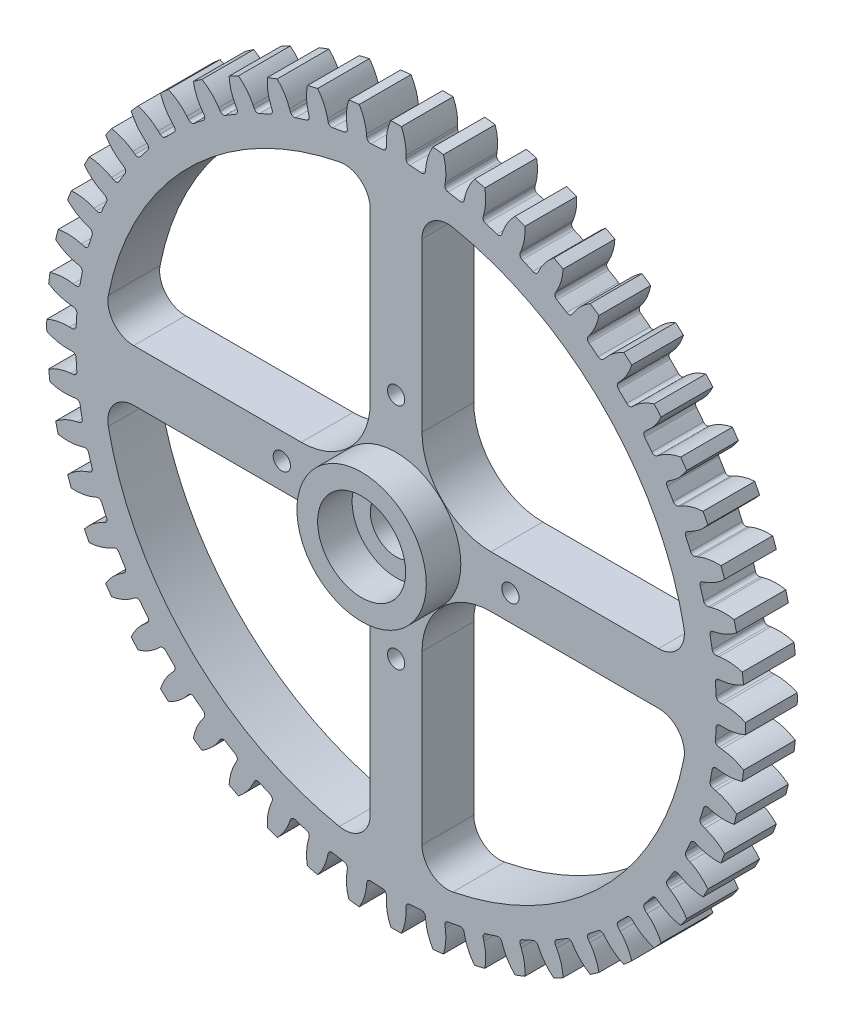
SolidWorks part; units mm, degrees
ref_plane "Front Plane" through (0, 0, 0) normal (0, 0, 1) x (1, 0, 0)
ref_plane "Top Plane" through (0, 0, 0) normal (0, 1, 0) x (1, 0, 0)
ref_plane "Right Plane" through (0, 0, 0) normal (1, 0, 0) x (0, 0, -1)
sketch "Esquisse1" plane through (0, 0, 0) normal (0, 0, 1) x (1, 0, 0)
  line L0 (0, 0) -> (22.1157, 0) construction
  line L1 (0, 0) -> (24.9555, 1.5095) construction
  line L2 (0, 0) -> (24.9555, -1.5095) construction
  line L3 (0, 0) -> (25.1466, 0.7599) construction
  line L4 (0, 0) -> (37.0573, 2.2416)
  line L5 (0, 0) -> (19.8775, -0.6006) construction
  line L6 (0, 0) -> (37.0573, -2.2416)
  line L7 (0, 0) -> (17.8277, 0.2693) construction
  line L8 (37.1081, 1.1213) -> (37.8577, 1.1439)
  line L9 (37.1081, -1.1213) -> (37.8577, -1.1439)
  line L10 (0, 0) -> (17.731, -0.2678) construction
  circle A0 centre (0, 0) radius 39 construction
  circle A1 centre (0, 0) radius 40.5 construction
  circle A2 centre (0, 0) radius 37.125 construction
  circle A3 centre (0, 0) radius 37.875 construction
  arc A4 (37.0573, 2.2416) -> (37.1081, 1.1213) centre (0, 0) cw
  arc A5 (37.0573, -2.2416) -> (37.1081, -1.1213) centre (0, 0) ccw
  arc A6 (37.8577, 1.1439) -> (40.4954, 0.6117) centre (38.0365, -4.7719) cw
  arc A7 (40.4954, 0.6117) -> (40.4954, -0.6117) centre (0, 0) cw
  arc A8 (37.8577, -1.1439) -> (40.4954, -0.6117) centre (38.0365, 4.7719) ccw
  dimension "PrimitiveDiameter" = 78
  dimension "OutsideDiameter" = 81
  dimension "InternalDiameter" = 74.25
  dimension "BaseDiameter" = 75.75
  dimension "DemiToothAngle" = 3.462
  dimension "QuartToothAngle" = 1.731
  dimension "D1" = 1.731
  dimension "D2" = 0.865
  dimension "D3" = 0.865
extrude "MainGear" add sketch "Esquisse1" along normal blind 6
fillet "Congé1" radius 0.45 2 edges at (37.1081, -1.1213, 3) (37.1081, 1.1213, 3)
ref_axis "Axe1" through (0, 0, 6) along (0, 0, -1)
pattern_circular "Répétition circulaire1" count 52 every 6.923 about axis through (0, 0, 6) along (0, 0, -1) of "MainGear", "Congé1"
sketch "Sketch1" plane through (0, 0, 6) normal (0, 0, 1) x (1, 0, 0)
  line L0 (3, 33.8674) -> (3, 3)
  line L1 (3, 3) -> (33.8674, 3)
  arc A0 (3, 33.8674) -> (33.8674, 3) centre (0, 0) cw
  dimension "D3" = 34
  dimension "D1" = 3
  dimension "D2" = 3
extrude "QuartSquareHole" cut sketch "Sketch1" against normal through all
sketch "Sketch3" plane through (0, 0, 6) normal (0, 0, 1) x (1, 0, 0)
  circle A0 centre (0, 0) radius 3
  dimension "D1" = 6
extrude "CentralHole" cut sketch "Sketch3" against normal through all
sketch "Sketch2" plane through (0, 0, 6) normal (0, 0, 1) x (1, 0, 0)
  circle A0 centre (13.25, 0) radius 1
  dimension "D1" = 2
  dimension "D2" = 13.25
extrude "ServoFixHole" cut sketch "Sketch2" against normal through all and the other way through all
pattern_circular "CirPattern1" count 4 every 90 about axis through (0, 0, 6) along (0, 0, -1) of "QuartSquareHole", "ServoFixHole"
fillet "Fillet1" radius 8 4 edges at (-3, 3, 3) (-3, -3, 3) (3, -3, 3) (3, 3, 3)
sketch "Sketch4" plane through (0, 0, 6) normal (0, 0, 1) x (1, 0, 0)
  circle A0 centre (0, 0) radius 7.5
  circle A1 centre (0, 0) radius 5.1
  dimension "D1" = 10.2
  dimension "D2" = 15
extrude "RollingBear10mmSupport" add sketch "Sketch4" along normal blind 4
fillet "Fillet5" radius 3 8 edges at (33.8674, -3, 3) (-33.8674, -3, 3) (-3, 33.8674, 3) (3, 33.8674, 3) (33.8674, 3, 3) (-3, -33.8674, 3) (3, -33.8674, 3) (-33.8674, 3, 3)
equation "\"Modulo\"= 1.5mm"
equation "\"ToothCount\" = 52"
equation "\"PrimitiveDiameter@Esquisse1\"= \"Modulo\" * \"ToothCount\""
equation "\"OutsideDiameter@Esquisse1\" = \"Modulo\" *  ( \"ToothCount\" + 2 ) "
equation "\"InternalDiameter@Esquisse1\" = \"PrimitiveDiameter@Esquisse1\" - \"Modulo\" * 2.5"
equation "\"Angle\"= 20deg"
equation "\"BaseDiameter@Esquisse1\"= \"PrimitiveDiameter@Esquisse1\" - \"Modulo\" * 1.5"
equation "\"DemiToothAngle@Esquisse1\" = 180 / \"ToothCount\""
equation "\"QuartToothAngle@Esquisse1\"= \"DemiToothAngle@Esquisse1\" / 2"
equation "\"D1@Esquisse1\"= \"QuartToothAngle@Esquisse1\""
equation "\"D2@Esquisse1\"= \"QuartToothAngle@Esquisse1\" / 2"
equation "\"D3@Esquisse1\"= \"D2@Esquisse1\""
equation "\"D2@Répétition circulaire1\"=360/\"ToothCount\""
equation "\"D1@Congé1\"=\"Modulo\"*0.3"
